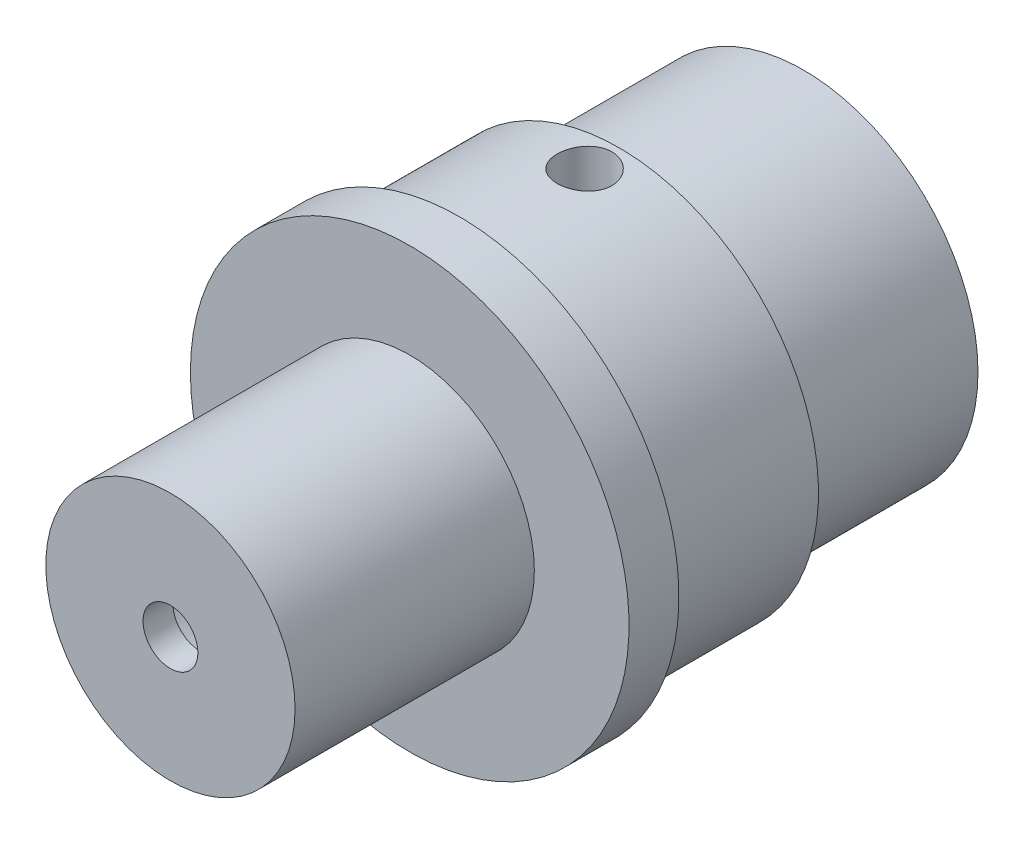
SolidWorks part; units mm, degrees
material "Polyethylene Cross-Linked"
ref_plane "Front Plane" through (0, 0, 0) normal (0, 0, 1) x (1, 0, 0)
ref_plane "Top Plane" through (0, 0, 0) normal (0, 1, 0) x (1, 0, 0)
ref_plane "Right Plane" through (0, 0, 0) normal (1, 0, 0) x (0, 0, -1)
sketch "Sketch2" plane through (0, 0, 0) normal (0, 0, 1) x (1, 0, 0)
  circle A0 centre (0, 0) radius 3.175
  dimension "D1" = 6.35
extrude "Boss-Extrude1" add sketch "Sketch2" against normal blind 6.096
sketch "Sketch3" plane through (0, 0, -6.096) normal (0, 0, -1) x (-1, 0, 0)
  circle A0 centre (0, 0) radius 5.588
  dimension "D1" = 11.176
extrude "Boss-Extrude2" add sketch "Sketch3" along normal blind 1.27
sketch "Sketch4" plane through (0, 0, -7.366) normal (0, 0, -1) x (-1, 0, 0)
  circle A0 centre (0, 0) radius 5.08
  dimension "D1" = 10.16
extrude "Boss-Extrude3" add sketch "Sketch4" along normal blind 4.064
sketch "Sketch5" plane through (0, 0, -11.43) normal (0, 0, -1) x (-1, 0, 0)
  circle A0 centre (0, 0) radius 4.445
  dimension "D1" = 8.89
extrude "Boss-Extrude4" add sketch "Sketch5" along normal blind 4.699
sketch "Sketch6" plane through (0, 0, -16.129) normal (0, 0, -1) x (-1, 0, 0)
  circle A0 centre (0, 0) radius 3.3655
  dimension "D1" = 6.731
extrude "Cut-Extrude1" cut sketch "Sketch6" against normal blind 7.112
sketch "Sketch7" plane through (0, 0, -9.017) normal (0, 0, -1) x (-1, 0, 0)
  circle A0 centre (0, 0) radius 2.2225
  dimension "D1" = 4.445
extrude "Cut-Extrude2" cut sketch "Sketch7" against normal blind 8.255
sketch "Sketch8" plane through (0, 0, 0) normal (0, 0, 1) x (1, 0, 0)
  circle A0 centre (0, 0) radius 0.6985
  dimension "D1" = 1.397
extrude "Cut-Extrude3" cut sketch "Sketch8" against normal through all
sketch "Sketch9" plane through (0, 0, 0) normal (0, 1, 0) x (1, 0, 0)
  line L0 (0, 16.129) -> (0, 10.55) construction
  line L1 (4.445, 16.129) -> (-4.445, 16.129) construction
  circle A0 centre (0, 10.55) radius 0.6985
  dimension "D1" = 1.397
  dimension "D2" = 5.579
extrude "Cut-Extrude4" cut sketch "Sketch9" against normal blind 8.255 and the other way blind 8.255
